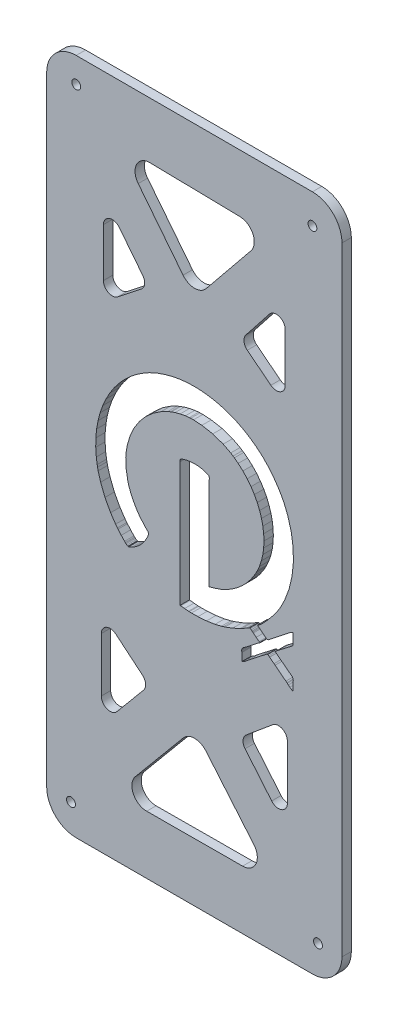
SolidWorks part; units mm, degrees
ref_plane "Front Plane" through (0, 0, 0) normal (0, 0, 1) x (1, 0, 0)
ref_plane "Top Plane" through (0, 0, 0) normal (0, 1, 0) x (1, 0, 0)
ref_plane "Right Plane" through (0, 0, 0) normal (1, 0, 0) x (0, 0, -1)
sketch "Sketch1" plane through (0, 0, 0) normal (0, 0, 1) x (1, 0, 0)
  line L0 (400.1785, -210.0802) -> (400.1634, -191.4944) construction
  line L1 (400.1634, -191.4944) -> (0.1636, -191.8187) construction
  line L2 (0.1636, -191.8187) -> (0.1786, -210.4045) construction
  line L3 (0.1786, -210.4045) -> (400.1785, -210.0802) construction
  line L4 (0, 19.2929) -> (0, 0.7071) construction
  line L5 (0, 0.7071) -> (400, 0.7071) construction
  line L6 (400, 0.7071) -> (400, 19.2929) construction
  line L7 (400, 19.2929) -> (0, 19.2929) construction
  line L8 (400.1785, -210.0802) -> (400.1634, -191.4944)
  line L9 (400.1634, -191.4944) -> (0.1636, -191.8187)
  line L10 (0.1636, -191.8187) -> (0.1786, -210.4045)
  line L11 (0.1786, -210.4045) -> (400.1785, -210.0802)
  line L12 (0, 19.2929) -> (0, 0.7071)
  line L13 (0, 0.7071) -> (400, 0.7071)
  line L14 (400, 0.7071) -> (400, 19.2929)
  line L15 (400, 19.2929) -> (0, 19.2929)
  line L17 (365, 19.2929) -> (265, 19.2929)
  line L18 (365, 19.2929) -> (365, -210.1898)
  line L19 (365, -210.1898) -> (265, -210.1898)
  line L20 (265, 19.2929) -> (265, -210.1898)
  circle A0 centre (355, 9.2929) radius 1.5
  circle A1 centre (275, 10.7822) radius 1.5
  circle A2 centre (356.8936, -200.1898) radius 1.5
  circle A3 centre (273.2443, -200.5469) radius 1.5
  dimension "D3" = 3
  dimension "D4" = 3
  dimension "D5" = 3
  dimension "D6" = 3
  dimension "D1" = 100
  dimension "D2" = 35
  dimension "D7" = 10
  dimension "D8" = 10
  dimension "D9" = 80
  dimension "D10" = 10
extrude "Boss-Extrude1" add sketch "Sketch1" along normal blind 3.175 contours L13 L20 L9 L18 | L15 L20 L13 L18 A1 A0 | L9 L20 L11 L18 A3 A2 region at (314.9995, -200.8601, 0) region at (314.9965, -95.4282, 0) region at (315, 9.9997, 0)
fillet "Fillet1" radius 10 4 edges at (365, -210.1087, 1.5875) (265, -210.1898, 1.5875) (265, 19.2929, 1.5875) (365, 19.2929, 1.5875)
sketch "Sketch4" plane through (0, 0, 3.175) normal (0, 0, 1) x (1, 0, 0)
  line L1 (277.2739, -95.4444) -> (300.7304, -95.4444) construction
  line L2 (265, -95.4444) -> (304.7293, -95.4444) construction
  line L3 (265, 9.2929) -> (265, -200.1817) construction
  line L4 (315.0081, -80.4042) -> (315.0081, -88.7022) construction
  line L5 (315.0081, -210.1492) -> (315.0081, -193.1318) construction
  line L6 (275.0081, -210.1816) -> (355.0081, -210.1168) construction
  line B0 (369.8783, -49.1421) -> (369.8783, -141.7466)
  line B1 (369.8783, -141.7466) -> (277.2739, -141.7466)
  line B2 (277.2739, -141.7466) -> (277.2739, -49.1421)
  line B3 (277.2739, -49.1421) -> (369.8783, -49.1421)
  line B4 (320.057, -114.0576) -> (320.057, -82.7575)
  line B5 (320.057, -82.7575) -> (320.057, -82.6307)
  line B6 (320.057, -82.6307) -> (320.0753, -82.2506)
  line B7 (320.0753, -82.2506) -> (320.0497, -81.8276)
  line B8 (320.0497, -81.8276) -> (320.0276, -81.7514)
  line B9 (320.0276, -81.7514) -> (320.0141, -81.7031)
  line B10 (320.0141, -81.7031) -> (319.9316, -81.57)
  line B11 (319.9316, -81.57) -> (319.7802, -81.4398)
  line B12 (319.7802, -81.4398) -> (319.5983, -81.3433)
  line B13 (319.5983, -81.3433) -> (319.456, -81.2821)
  line B14 (319.456, -81.2821) -> (319.4087, -81.2618)
  line B15 (319.4087, -81.2618) -> (319.2814, -81.2064)
  line B16 (319.2814, -81.2064) -> (317.9691, -80.7698)
  line B17 (317.9691, -80.7698) -> (317.8345, -80.7346)
  line B18 (317.8345, -80.7346) -> (317.493, -80.6445)
  line B19 (317.493, -80.6445) -> (316.4421, -80.4752)
  line B20 (316.4421, -80.4752) -> (315.0081, -80.4042)
  line B21 (315.0081, -80.4042) -> (313.5752, -80.5094)
  line B22 (313.5752, -80.5094) -> (312.5281, -80.6908)
  line B23 (312.5281, -80.6908) -> (312.1856, -80.7785)
  line B24 (312.1856, -80.7785) -> (312.0694, -80.808)
  line B25 (312.0694, -80.808) -> (311.7183, -80.8943)
  line B26 (311.7183, -80.8943) -> (311.1863, -81.0468)
  line B27 (311.1863, -81.0468) -> (310.6818, -81.2517)
  line B28 (310.6818, -81.2517) -> (310.3761, -81.4412)
  line B29 (310.3761, -81.4412) -> (310.2969, -81.5256)
  line B30 (310.2969, -81.5256) -> (310.2608, -81.5642)
  line B31 (310.2608, -81.5642) -> (310.1874, -81.7138)
  line B32 (310.1874, -81.7138) -> (310.1459, -81.9351)
  line B33 (310.1459, -81.9351) -> (310.1431, -82.1676)
  line B34 (310.1431, -82.1676) -> (310.1484, -82.3321)
  line B35 (310.1484, -82.3321) -> (310.1484, -82.387)
  line B36 (310.1484, -82.387) -> (310.1484, -124.4293)
  line B37 (310.1484, -124.4293) -> (310.4117, -124.4313)
  line B38 (310.4117, -124.4313) -> (311.7226, -124.561)
  line B39 (311.7226, -124.561) -> (313.034, -124.699)
  line B40 (313.034, -124.699) -> (313.2969, -124.7056)
  line B41 (313.2969, -124.7056) -> (314.0296, -124.7236)
  line B42 (314.0296, -124.7236) -> (316.2293, -124.6932)
  line B43 (316.2293, -124.6932) -> (319.1436, -124.4843)
  line B44 (319.1436, -124.4843) -> (322.0287, -124.0392)
  line B45 (322.0287, -124.0392) -> (324.1731, -123.5327)
  line B46 (324.1731, -123.5327) -> (324.8725, -123.3156)
  line B47 (324.8725, -123.3156) -> (325.402, -123.1508)
  line B48 (325.402, -123.1508) -> (327.9843, -122.189)
  line B49 (327.9843, -122.189) -> (330.4919, -121.0478)
  line B50 (330.4919, -121.0478) -> (330.9843, -120.7937)
  line B51 (330.9843, -120.7937) -> (331.1425, -120.7122)
  line B52 (331.1425, -120.7122) -> (332.6849, -119.817)
  line B53 (332.6849, -119.817) -> (332.8364, -119.7239)
  line B54 (332.8364, -119.7239) -> (332.8967, -119.6868)
  line B55 (332.8967, -119.6868) -> (333.2333, -119.4528)
  line B56 (333.2333, -119.4528) -> (333.5965, -119.285)
  line B57 (333.5965, -119.285) -> (333.6698, -119.2811)
  line B58 (333.6698, -119.2811) -> (333.7437, -119.2769)
  line B59 (333.7437, -119.2769) -> (333.9699, -119.3472)
  line B60 (333.9699, -119.3472) -> (334.266, -119.5304)
  line B61 (334.266, -119.5304) -> (334.5423, -119.7601)
  line B62 (334.5423, -119.7601) -> (334.7194, -119.9163)
  line B63 (334.7194, -119.9163) -> (334.7811, -119.965)
  line B64 (334.7811, -119.965) -> (334.9726, -120.1146)
  line B65 (334.9726, -120.1146) -> (335.9454, -120.9162)
  line B66 (335.9454, -120.9162) -> (336.9712, -121.6353)
  line B67 (336.9712, -121.6353) -> (337.1887, -121.7438)
  line B68 (337.1887, -121.7438) -> (337.1887, -121.929)
  line B69 (337.1887, -121.929) -> (337.0731, -121.9778)
  line B70 (337.0731, -121.9778) -> (336.7422, -122.1663)
  line B71 (336.7422, -122.1663) -> (336.3212, -122.4644)
  line B72 (336.3212, -122.4644) -> (335.9174, -122.7908)
  line B73 (335.9174, -122.7908) -> (335.6222, -123.0345)
  line B74 (335.6222, -123.0345) -> (335.5219, -123.1136)
  line B75 (335.5219, -123.1136) -> (332.6512, -125.3554)
  line B76 (332.6512, -125.3554) -> (332.5571, -125.4292)
  line B77 (332.5571, -125.4292) -> (332.2591, -125.6312)
  line B78 (332.2591, -125.6312) -> (331.8096, -125.9413)
  line B79 (331.8096, -125.9413) -> (331.401, -126.2863)
  line B80 (331.401, -126.2863) -> (331.1763, -126.5626)
  line B81 (331.1763, -126.5626) -> (331.1329, -126.6677)
  line B82 (331.1329, -126.6677) -> (331.1063, -126.7328)
  line B83 (331.1063, -126.7328) -> (331.0653, -126.9456)
  line B84 (331.0653, -126.9456) -> (331.0528, -127.2538)
  line B85 (331.0528, -127.2538) -> (331.0663, -127.5658)
  line B86 (331.0663, -127.5658) -> (331.0769, -127.7828)
  line B87 (331.0769, -127.7828) -> (331.0769, -127.8557)
  line B88 (331.0769, -127.8557) -> (331.0769, -130.4486)
  line B89 (331.0769, -130.4486) -> (331.2747, -130.397)
  line B90 (331.2747, -130.397) -> (332.2016, -129.8183)
  line B91 (332.2016, -129.8183) -> (333.0491, -129.0924)
  line B92 (333.0491, -129.0924) -> (333.2068, -128.9674)
  line B93 (333.2068, -128.9674) -> (333.5593, -128.6876)
  line B94 (333.5593, -128.6876) -> (337.1131, -125.9298)
  line B95 (337.1131, -125.9298) -> (337.4666, -125.6524)
  line B96 (337.4666, -125.6524) -> (337.5979, -125.5492)
  line B97 (337.5979, -125.5492) -> (338.9088, -124.5195)
  line B98 (338.9088, -124.5195) -> (339.0409, -124.4182)
  line B99 (339.0409, -124.4182) -> (339.0829, -124.3864)
  line B100 (339.0829, -124.3864) -> (339.2038, -124.2861)
  line B101 (339.2038, -124.2861) -> (339.3838, -124.149)
  line B102 (339.3838, -124.149) -> (339.5778, -124.0435)
  line B103 (339.5778, -124.0435) -> (339.7316, -124.0049)
  line B104 (339.7316, -124.0049) -> (339.7817, -124.0073)
  line B105 (339.7817, -124.0073) -> (339.8507, -124.0106)
  line B106 (339.8507, -124.0106) -> (340.1792, -124.1732)
  line B107 (340.1792, -124.1732) -> (340.4719, -124.4086)
  line B108 (340.4719, -124.4086) -> (340.5225, -124.4486)
  line B109 (340.5225, -124.4486) -> (342.0042, -125.6009)
  line B110 (342.0042, -125.6009) -> (342.3683, -125.8826)
  line B111 (342.3683, -125.8826) -> (345.993, -128.7175)
  line B112 (345.993, -128.7175) -> (346.3566, -128.9993)
  line B113 (346.3566, -128.9993) -> (346.4825, -129.0962)
  line B114 (346.4825, -129.0962) -> (346.8457, -129.4059)
  line B115 (346.8457, -129.4059) -> (347.3626, -129.837)
  line B116 (347.3626, -129.837) -> (347.9091, -130.2113)
  line B117 (347.9091, -130.2113) -> (348.337, -130.4129)
  line B118 (348.337, -130.4129) -> (348.4865, -130.4486)
  line B119 (348.4865, -130.4486) -> (348.4865, -127.9483)
  line B120 (348.4865, -127.9483) -> (348.4865, -127.8745)
  line B121 (348.4865, -127.8745) -> (348.4966, -127.6531)
  line B122 (348.4966, -127.6531) -> (348.5087, -127.3401)
  line B123 (348.5087, -127.3401) -> (348.4956, -127.03)
  line B124 (348.4956, -127.03) -> (348.4561, -126.8129)
  line B125 (348.4561, -126.8129) -> (348.4306, -126.7459)
  line B126 (348.4306, -126.7459) -> (348.3871, -126.6306)
  line B127 (348.3871, -126.6306) -> (348.1523, -126.3249)
  line B128 (348.1523, -126.3249) -> (347.7226, -125.9492)
  line B129 (347.7226, -125.9492) -> (347.2441, -125.6149)
  line B130 (347.2441, -125.6149) -> (346.9219, -125.3959)
  line B131 (346.9219, -125.3959) -> (346.8196, -125.3164)
  line B132 (346.8196, -125.3164) -> (346.5804, -125.1297)
  line B133 (346.5804, -125.1297) -> (344.189, -123.2583)
  line B134 (344.189, -123.2583) -> (343.9489, -123.0726)
  line B135 (343.9489, -123.0726) -> (343.8221, -122.9742)
  line B136 (343.8221, -122.9742) -> (343.1863, -122.463)
  line B137 (343.1863, -122.463) -> (342.5183, -122.0024)
  line B138 (342.5183, -122.0024) -> (342.3746, -121.929)
  line B139 (342.3746, -121.929) -> (342.4484, -121.8326)
  line B140 (342.4484, -121.8326) -> (342.7012, -121.5677)
  line B141 (342.7012, -121.5677) -> (343.0729, -121.2466)
  line B142 (343.0729, -121.2466) -> (343.4661, -120.947)
  line B143 (343.4661, -120.947) -> (343.7603, -120.7272)
  line B144 (343.7603, -120.7272) -> (343.8562, -120.6518)
  line B145 (343.8562, -120.6518) -> (344.1022, -120.459)
  line B146 (344.1022, -120.459) -> (346.5737, -118.5485)
  line B147 (346.5737, -118.5485) -> (346.8196, -118.3565)
  line B148 (346.8196, -118.3565) -> (346.9185, -118.2793)
  line B149 (346.9185, -118.2793) -> (347.2277, -118.0667)
  line B150 (347.2277, -118.0667) -> (347.6781, -117.7527)
  line B151 (347.6781, -117.7527) -> (348.092, -117.4059)
  line B152 (348.092, -117.4059) -> (348.3355, -117.1242)
  line B153 (348.3355, -117.1242) -> (348.3914, -117.0177)
  line B154 (348.3914, -117.0177) -> (348.4253, -116.9535)
  line B155 (348.4253, -116.9535) -> (348.4812, -116.7394)
  line B156 (348.4812, -116.7394) -> (348.5057, -116.4287)
  line B157 (348.5057, -116.4287) -> (348.4966, -116.1128)
  line B158 (348.4966, -116.1128) -> (348.4865, -115.891)
  line B159 (348.4865, -115.891) -> (348.4865, -115.8171)
  line B160 (348.4865, -115.8171) -> (348.4865, -113.2242)
  line B161 (348.4865, -113.2242) -> (348.338, -113.2464)
  line B162 (348.338, -113.2464) -> (347.9081, -113.4268)
  line B163 (347.9081, -113.4268) -> (347.356, -113.7928)
  line B164 (347.356, -113.7928) -> (346.8365, -114.2269)
  line B165 (346.8365, -114.2269) -> (346.48, -114.5357)
  line B166 (346.48, -114.5357) -> (346.3566, -114.6331)
  line B167 (346.3566, -114.6331) -> (345.9943, -114.9181)
  line B168 (345.9943, -114.9181) -> (342.3655, -117.77)
  line B169 (342.3655, -117.77) -> (342.0042, -118.058)
  line B170 (342.0042, -118.058) -> (341.8744, -118.1612)
  line B171 (341.8744, -118.1612) -> (340.5615, -119.1808)
  line B172 (340.5615, -119.1808) -> (340.43, -119.2826)
  line B173 (340.43, -119.2826) -> (340.389, -119.3144)
  line B174 (340.389, -119.3144) -> (340.2679, -119.4142)
  line B175 (340.2679, -119.4142) -> (340.0894, -119.5474)
  line B176 (340.0894, -119.5474) -> (339.8966, -119.642)
  line B177 (339.8966, -119.642) -> (339.7392, -119.668)
  line B178 (339.7392, -119.668) -> (339.6891, -119.6602)
  line B179 (339.6891, -119.6602) -> (339.6187, -119.6491)
  line B180 (339.6187, -119.6491) -> (339.4161, -119.556)
  line B181 (339.4161, -119.556) -> (339.1494, -119.3675)
  line B182 (339.1494, -119.3675) -> (338.8977, -119.1484)
  line B183 (338.8977, -119.1484) -> (338.7297, -118.9999)
  line B184 (338.7297, -118.9999) -> (338.6704, -118.9546)
  line B185 (338.6704, -118.9546) -> (338.4761, -118.8045)
  line B186 (338.4761, -118.8045) -> (336.541, -117.2748)
  line B187 (336.541, -117.2748) -> (336.3553, -117.1136)
  line B188 (336.3553, -117.1136) -> (336.5792, -116.9979)
  line B189 (336.5792, -116.9979) -> (337.2027, -116.5604)
  line B190 (337.2027, -116.5604) -> (338.0009, -115.8587)
  line B191 (338.0009, -115.8587) -> (338.7448, -115.0892)
  line B192 (338.7448, -115.0892) -> (339.2569, -114.5236)
  line B193 (339.2569, -114.5236) -> (339.4272, -114.3355)
  line B194 (339.4272, -114.3355) -> (339.8045, -113.9188)
  line B195 (339.8045, -113.9188) -> (341.5947, -111.7884)
  line B196 (341.5947, -111.7884) -> (343.2273, -109.535)
  line B197 (343.2273, -109.535) -> (343.5249, -109.057)
  line B198 (343.5249, -109.057) -> (344.0984, -108.1368)
  line B199 (344.0984, -108.1368) -> (345.571, -105.2231)
  line B200 (345.571, -105.2231) -> (347.0931, -101.1698)
  line B201 (347.0931, -101.1698) -> (348.0866, -96.9621)
  line B202 (348.0866, -96.9621) -> (348.5463, -92.6661)
  line B203 (348.5463, -92.6661) -> (348.4672, -88.3465)
  line B204 (348.4672, -88.3465) -> (347.8436, -84.0694)
  line B205 (347.8436, -84.0694) -> (346.6711, -79.9002)
  line B206 (346.6711, -79.9002) -> (345.4417, -76.8694)
  line B207 (345.4417, -76.8694) -> (344.9434, -75.9048)
  line B208 (344.9434, -75.9048) -> (344.6029, -75.2439)
  line B209 (344.6029, -75.2439) -> (343.4661, -73.321)
  line B210 (343.4661, -73.321) -> (341.7654, -70.8674)
  line B211 (341.7654, -70.8674) -> (339.8541, -68.5751)
  line B212 (339.8541, -68.5751) -> (338.2957, -66.9733)
  line B213 (338.2957, -66.9733) -> (337.7444, -66.4751)
  line B214 (337.7444, -66.4751) -> (337.2732, -66.0482)
  line B215 (337.2732, -66.0482) -> (335.7929, -64.8414)
  line B216 (335.7929, -64.8414) -> (333.7374, -63.3738)
  line B217 (333.7374, -63.3738) -> (331.589, -62.0734)
  line B218 (331.589, -62.0734) -> (329.3594, -60.9419)
  line B219 (329.3594, -60.9419) -> (327.0597, -59.9807)
  line B220 (327.0597, -59.9807) -> (324.7007, -59.1911)
  line B221 (324.7007, -59.1911) -> (322.2935, -58.5752)
  line B222 (322.2935, -58.5752) -> (319.85, -58.1349)
  line B223 (319.85, -58.1349) -> (317.3816, -57.8711)
  line B224 (317.3816, -57.8711) -> (314.8987, -57.7862)
  line B225 (314.8987, -57.7862) -> (312.4129, -57.8807)
  line B226 (312.4129, -57.8807) -> (309.9351, -58.1576)
  line B227 (309.9351, -58.1576) -> (307.4773, -58.6172)
  line B228 (307.4773, -58.6172) -> (305.0498, -59.2615)
  line B229 (305.0498, -59.2615) -> (302.6649, -60.0926)
  line B230 (302.6649, -60.0926) -> (300.9048, -60.8349)
  line B231 (300.9048, -60.8349) -> (300.3323, -61.1122)
  line B232 (300.3323, -61.1122) -> (299.7015, -61.4175)
  line B233 (299.7015, -61.4175) -> (297.8619, -62.4443)
  line B234 (297.8619, -62.4443) -> (295.5396, -63.9718)
  line B235 (295.5396, -63.9718) -> (293.373, -65.6798)
  line B236 (293.373, -65.6798) -> (291.3676, -67.554)
  line B237 (291.3676, -67.554) -> (289.5304, -69.5806)
  line B238 (289.5304, -69.5806) -> (287.8674, -71.7449)
  line B239 (287.8674, -71.7449) -> (286.3852, -74.0334)
  line B240 (286.3852, -74.0334) -> (285.0903, -76.431)
  line B241 (285.0903, -76.431) -> (283.9886, -78.924)
  line B242 (283.9886, -78.924) -> (283.0872, -81.4982)
  line B243 (283.0872, -81.4982) -> (282.3922, -84.1392)
  line B244 (282.3922, -84.1392) -> (281.9104, -86.833)
  line B245 (281.9104, -86.833) -> (281.647, -89.5659)
  line B246 (281.647, -89.5659) -> (281.6099, -92.3222)
  line B247 (281.6099, -92.3222) -> (281.8047, -95.0892)
  line B248 (281.8047, -95.0892) -> (282.0999, -97.1671)
  line B249 (282.0999, -97.1671) -> (282.2374, -97.852)
  line B250 (282.2374, -97.852) -> (282.4361, -98.8372)
  line B251 (282.4361, -98.8372) -> (283.2661, -101.7471)
  line B252 (283.2661, -101.7471) -> (284.744, -105.4783)
  line B253 (284.744, -105.4783) -> (286.6544, -109.0079)
  line B254 (286.6544, -109.0079) -> (288.3512, -111.5131)
  line B255 (288.3512, -111.5131) -> (288.9792, -112.2982)
  line B256 (288.9792, -112.2982) -> (289.1836, -112.5538)
  line B257 (289.1836, -112.5538) -> (290.2505, -113.8242)
  line B258 (290.2505, -113.8242) -> (291.3878, -115.03)
  line B259 (291.3878, -115.03) -> (291.6275, -115.2533)
  line B260 (291.6275, -115.2533) -> (291.6921, -115.3132)
  line B261 (291.6921, -115.3132) -> (291.8823, -115.4959)
  line B262 (291.8823, -115.4959) -> (292.1701, -115.7346)
  line B263 (292.1701, -115.7346) -> (292.4875, -115.8963)
  line B264 (292.4875, -115.8963) -> (292.7514, -115.928)
  line B265 (292.7514, -115.928) -> (292.8314, -115.9088)
  line B266 (292.8314, -115.9088) -> (292.9838, -115.8712)
  line B267 (292.9838, -115.8712) -> (293.7405, -115.5475)
  line B268 (293.7405, -115.5475) -> (294.4583, -115.1376)
  line B269 (294.4583, -115.1376) -> (294.5909, -115.0576)
  line B270 (294.5909, -115.0576) -> (294.902, -114.8694)
  line B271 (294.902, -114.8694) -> (295.7856, -114.2231)
  line B272 (295.7856, -114.2231) -> (296.8582, -113.243)
  line B273 (296.8582, -113.243) -> (297.7958, -112.1332)
  line B274 (297.7958, -112.1332) -> (298.4083, -111.2264)
  line B275 (298.4083, -111.2264) -> (298.5854, -110.9092)
  line B276 (298.5854, -110.9092) -> (298.6563, -110.7823)
  line B277 (298.6563, -110.7823) -> (298.8709, -110.4031)
  line B278 (298.8709, -110.4031) -> (299.1834, -109.7906)
  line B279 (299.1834, -109.7906) -> (299.4159, -109.1578)
  line B280 (299.4159, -109.1578) -> (299.4839, -108.7291)
  line B281 (299.4839, -108.7291) -> (299.4607, -108.594)
  line B282 (299.4607, -108.594) -> (299.4472, -108.5105)
  line B283 (299.4472, -108.5105) -> (299.3329, -108.2737)
  line B284 (299.3329, -108.2737) -> (299.1019, -107.9835)
  line B285 (299.1019, -107.9835) -> (298.8284, -107.7206)
  line B286 (298.8284, -107.7206) -> (298.6346, -107.544)
  line B287 (298.6346, -107.544) -> (298.5728, -107.4828)
  line B288 (298.5728, -107.4828) -> (298.3905, -107.3)
  line B289 (298.3905, -107.3) -> (296.7033, -105.3736)
  line B290 (296.7033, -105.3736) -> (296.5477, -105.1676)
  line B291 (296.5477, -105.1676) -> (296.2162, -104.7287)
  line B292 (296.2162, -104.7287) -> (295.2984, -103.3527)
  line B293 (295.2984, -103.3527) -> (294.2118, -101.4205)
  line B294 (294.2118, -101.4205) -> (293.3152, -99.3939)
  line B295 (293.3152, -99.3939) -> (292.7764, -97.8283)
  line B296 (292.7764, -97.8283) -> (292.6355, -97.2963)
  line B297 (292.6355, -97.2963) -> (292.4736, -96.6814)
  line B298 (292.4736, -96.6814) -> (291.9193, -93.5319)
  line B299 (291.9193, -93.5319) -> (291.7776, -90.3394)
  line B300 (291.7776, -90.3394) -> (291.8209, -89.7028)
  line B301 (291.8209, -89.7028) -> (291.8783, -88.863)
  line B302 (291.8783, -88.863) -> (292.299, -86.3608)
  line B303 (292.299, -86.3608) -> (293.2433, -83.1641)
  line B304 (293.2433, -83.1641) -> (294.6212, -80.153)
  line B305 (294.6212, -80.153) -> (296.3981, -77.3676)
  line B306 (296.3981, -77.3676) -> (298.5395, -74.8504)
  line B307 (298.5395, -74.8504) -> (301.0124, -72.6409)
  line B308 (301.0124, -72.6409) -> (303.7823, -70.7811)
  line B309 (303.7823, -70.7811) -> (306.0347, -69.6231)
  line B310 (306.0347, -69.6231) -> (306.8146, -69.3116)
  line B311 (306.8146, -69.3116) -> (307.226, -69.1471)
  line B312 (307.226, -69.1471) -> (308.4829, -68.712)
  line B313 (308.4829, -68.712) -> (310.2212, -68.2316)
  line B314 (310.2212, -68.2316) -> (311.9923, -67.9023)
  line B315 (311.9923, -67.9023) -> (313.3177, -67.7677)
  line B316 (313.3177, -67.7677) -> (313.76, -67.7571)
  line B317 (313.76, -67.7571) -> (314.7106, -67.7334)
  line B318 (314.7106, -67.7334) -> (317.5688, -67.9104)
  line B319 (317.5688, -67.9104) -> (321.2416, -68.5852)
  line B320 (321.2416, -68.5852) -> (324.7619, -69.8199)
  line B321 (324.7619, -69.8199) -> (327.3183, -71.1293)
  line B322 (327.3183, -71.1293) -> (328.1136, -71.6522)
  line B323 (328.1136, -71.6522) -> (328.5645, -71.9484)
  line B324 (328.5645, -71.9484) -> (329.8591, -72.9235)
  line B325 (329.8591, -72.9235) -> (331.4584, -74.3411)
  line B326 (331.4584, -74.3411) -> (332.9078, -75.8898)
  line B327 (332.9078, -75.8898) -> (334.2023, -77.5562)
  line B328 (334.2023, -77.5562) -> (335.3386, -79.3258)
  line B329 (335.3386, -79.3258) -> (336.3118, -81.1846)
  line B330 (336.3118, -81.1846) -> (337.1179, -83.1182)
  line B331 (337.1179, -83.1182) -> (337.7522, -85.1126)
  line B332 (337.7522, -85.1126) -> (338.2113, -87.1533)
  line B333 (338.2113, -87.1533) -> (338.4901, -89.2268)
  line B334 (338.4901, -89.2268) -> (338.5847, -91.3185)
  line B335 (338.5847, -91.3185) -> (338.491, -93.4147)
  line B336 (338.491, -93.4147) -> (338.2046, -95.5002)
  line B337 (338.2046, -95.5002) -> (337.7213, -97.5621)
  line B338 (337.7213, -97.5621) -> (337.0364, -99.5853)
  line B339 (337.0364, -99.5853) -> (336.3925, -101.0752)
  line B340 (336.3925, -101.0752) -> (336.146, -101.5561)
  line B341 (336.146, -101.5561) -> (335.9136, -102.0104)
  line B342 (335.9136, -102.0104) -> (335.1366, -103.3339)
  line B343 (335.1366, -103.3339) -> (333.9863, -105.009)
  line B344 (333.9863, -105.009) -> (332.7037, -106.575)
  line B345 (332.7037, -106.575) -> (331.2973, -108.0258)
  line B346 (331.2973, -108.0258) -> (329.7751, -109.3547)
  line B347 (329.7751, -109.3547) -> (328.145, -110.5552)
  line B348 (328.145, -110.5552) -> (326.4153, -111.6216)
  line B349 (326.4153, -111.6216) -> (325.0586, -112.3348)
  line B350 (325.0586, -112.3348) -> (324.5946, -112.5476)
  line B351 (324.5946, -112.5476) -> (324.2261, -112.7164)
  line B352 (324.2261, -112.7164) -> (322.3432, -113.3622)
  line B353 (322.3432, -113.3622) -> (320.4371, -113.9284)
  line B354 (320.4371, -113.9284) -> (320.057, -114.0576)
  line B355 (337.6518, -121.7438) -> (337.7502, -121.8721)
  line B356 (337.7502, -121.8721) -> (338.3497, -122.4355)
  line B357 (338.3497, -122.4355) -> (339.0067, -122.9403)
  line B358 (339.0067, -122.9403) -> (339.1334, -123.0397)
  line B359 (339.1334, -123.0397) -> (339.1788, -123.0749)
  line B360 (339.1788, -123.0749) -> (339.4325, -123.2685)
  line B361 (339.4325, -123.2685) -> (339.72, -123.3851)
  line B362 (339.72, -123.3851) -> (339.7817, -123.3826)
  line B363 (339.7817, -123.3826) -> (339.8439, -123.3798)
  line B364 (339.8439, -123.3798) -> (340.1304, -123.2429)
  line B365 (340.1304, -123.2429) -> (340.3846, -123.0388)
  line B366 (340.3846, -123.0388) -> (340.43, -123.0031)
  line B367 (340.43, -123.0031) -> (340.5447, -122.9125)
  line B368 (340.5447, -122.9125) -> (341.7018, -122.0158)
  line B369 (341.7018, -122.0158) -> (341.819, -121.929)
  line B370 (341.819, -121.929) -> (341.7651, -121.822)
  line B371 (341.7651, -121.822) -> (341.5368, -121.5335)
  line B372 (341.5368, -121.5335) -> (341.1587, -121.1902)
  line B373 (341.1587, -121.1902) -> (340.7406, -120.8823)
  line B374 (340.7406, -120.8823) -> (340.4362, -120.6682)
  line B375 (340.4362, -120.6682) -> (340.3373, -120.594)
  line B376 (340.3373, -120.594) -> (340.291, -120.5587)
  line B377 (340.291, -120.5587) -> (340.0388, -120.377)
  line B378 (340.0388, -120.377) -> (339.7528, -120.2862)
  line B379 (339.7528, -120.2862) -> (339.6891, -120.2964)
  line B380 (339.6891, -120.2964) -> (339.6201, -120.3075)
  line B381 (339.6201, -120.3075) -> (339.2946, -120.4921)
  line B382 (339.2946, -120.4921) -> (339.0013, -120.7372)
  line B383 (339.0013, -120.7372) -> (338.9483, -120.7787)
  line B384 (338.9483, -120.7787) -> (338.8422, -120.8612)
  line B385 (338.8422, -120.8612) -> (338.3121, -121.2779)
  line B386 (338.3121, -121.2779) -> (337.7662, -121.6725)
  line B387 (337.7662, -121.6725) -> (337.6518, -121.7438)
sketch_block_instance "Block1-1"
sketch_block "Block1"
extrude "Cut-Extrude1" cut sketch "Sketch4" against normal blind 10 contours B353 B354 B4 B5 B6 B7 B8 B9 B10 B11 B12 B13 B14 B15 B16 B17 B18 B19 B20 B21 B22 B23 B24 B25 B26 B27 B28 B29 B30 B31 B32 B33 B34 B35 B36 B37 B38 B39 B40 B41 B42 B43 B44 B45 B46 B47 B48 B49 B50 B51 B52 | B386 B387 B355 B356 B357 B358 B359 B360 B361 B362 B363 B364 B365 B366 B367 B368 B369 B370 B371 B372 B373 B374 B375 B376 B377 B378 B379 B380 B381 B382 B383 B384 B385 region at (317.2255, -92.0463, 3.175) region at (339.7634, -121.8326, 3.175)
sketch "Sketch5" plane through (0, 0, 3.175) normal (0, 0, 1) x (1, 0, 0)
  line L0 (355, 9.2929) -> (275, 10.7822)
  line L1 (356.8936, -200.1898) -> (273.2443, -200.5469)
  line L2 (315.0689, -200.3683) -> (315.0689, -150.3683)
  line L3 (315.0689, -150.3683) -> (356.8936, -200.1898)
  line L4 (273.2443, -200.5469) -> (315.0689, -150.3683)
  line L5 (315, 10.0375) -> (315, -39.9625)
  line L6 (315, -39.9625) -> (355, 9.2929)
  line L7 (275, 10.7822) -> (315, -39.9625)
  line L8 (315.0581, -31.9594) -> (344.6542, 4.4846)
  line L10 (285.4621, 5.5865) -> (315.0581, -31.9594)
  line L11 (315.0826, -158.1611) -> (346.2061, -195.2353)
  line L13 (283.9591, -195.5011) -> (315.0826, -158.1611)
  line L14 (344.6542, 4.4846) -> (285.4621, 5.5865) construction
  line L15 (346.2061, -195.2353) -> (283.9591, -195.5011) construction
  line L16 (354.8139, -0.7054) -> (274.8139, 0.7839)
  line L17 (356.8509, -190.1899) -> (273.2016, -190.547)
  dimension "D1" = 50
  dimension "D2" = 50
  dimension "D3" = 5
  dimension "D4" = 5
  dimension "D5" = 10
  dimension "D6" = 10
extrude "Cut-Extrude2" cut sketch "Sketch5" against normal through all contours L5 L10 L8 | L10 L5 | L13 L2 L11 | L13 L2 region at (323.5512, -10.8121, 3.175) region at (306.4876, -10.4462, 3.175) region at (306.0932, -179.6763, 3.175) region at (324.0538, -179.5888, 3.175)
fillet "Fillet2" radius 5 6 edges at (288.1416, -190.4832, 1.5875) (315.0826, -158.1611, 1.5875) (342.0236, -190.2532, 1.5875) (289.4628, 0.5112, 1.5875) (315.0581, -31.9594, 1.5875) (340.6535, -0.4418, 1.5875)
sketch "Sketch6" plane through (0, 0, 3.175) normal (0, 0, 1) x (1, 0, 0)
  line L5 (284.218, -17.0656) -> (299.4094, -36.3375)
  line L6 (284.218, -17.0656) -> (299.4094, -36.3375)
  line L8 (283.4935, -172.6321) -> (299.7333, -153.1486)
  line L9 (283.4935, -172.6321) -> (299.7333, -153.1486)
  line L10 (284.218, -54.4841) -> (284.218, -17.0656)
  line L11 (299.7333, -153.1486) -> (283.4935, -139.6125)
  line L12 (283.4935, -139.6125) -> (283.4935, -172.6321)
  line L13 (299.4094, -36.3375) -> (284.218, -48.3123)
  dimension "D1" = 15
  dimension "D2" = 15
extrude "Cut-Extrude3" cut sketch "Sketch6" against normal blind 10 contours L13 L6 L10 | L11 L12 L9 region at (289.2818, -33.9051, 3.175) region at (288.9067, -155.131, 3.175)
fillet "Fillet3" radius 3 6 edges at (283.4935, -172.6321, 1.5875) (283.4935, -139.6125, 1.5875) (299.7333, -153.1486, 1.5875) (284.218, -48.3123, 1.5875) (284.218, -17.0656, 1.5875) (299.4094, -36.3375, 1.5875)
ref_plane "Plane2" through (315, 0, 0) normal (1, 0, 0) x (0, 0, -1)
mirror "Mirror1" about plane through (315, 0, 0) normal (1, 0, 0) of "Fillet3", "Cut-Extrude3"
